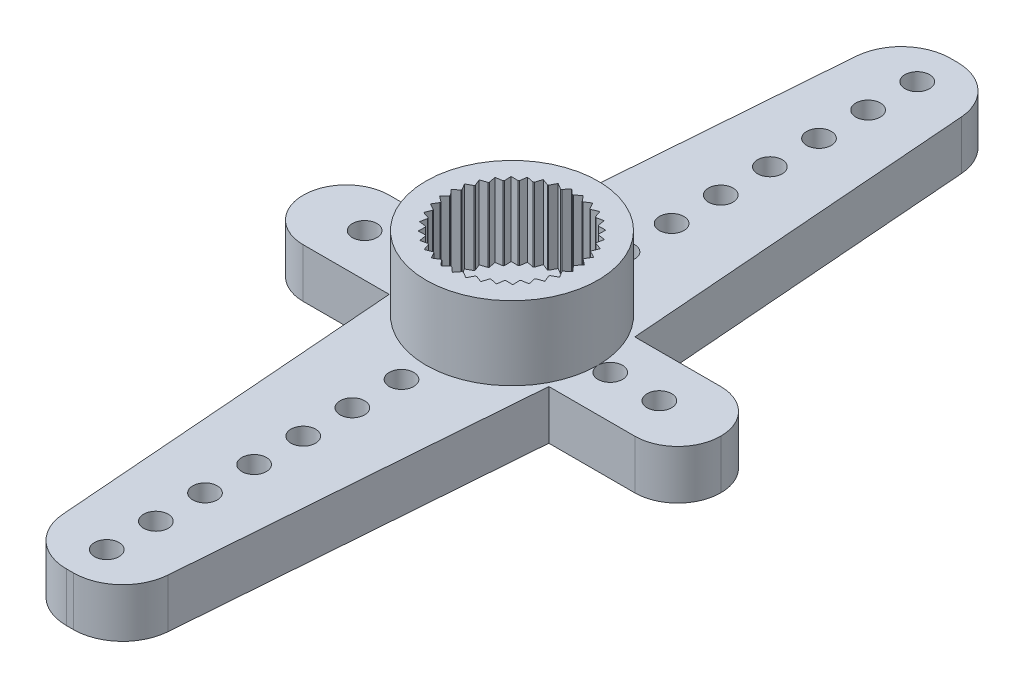
SolidWorks part; units mm, degrees
ref_plane "Front Plane" through (0, 0, 0) normal (0, 0, 1) x (1, 0, 0)
ref_plane "Top Plane" through (0, 0, 0) normal (0, 1, 0) x (1, 0, 0)
ref_plane "Right Plane" through (0, 0, 0) normal (1, 0, 0) x (0, 0, -1)
sketch "Sketch1" plane through (0, 0, 0) normal (0, 1, 0) x (1, 0, 0)
  line L0 (-21.777, 0) -> (33.3507, 0) construction
  line L1 (0, 26.1309) -> (0, -34.4991) construction
  line L2 (-17.4191, 18) -> (29.5794, 18) construction
  line L3 (-18.8664, -18) -> (33.3507, -18) construction
  line L4 (8.5, 26.926) -> (8.5, -27.618) construction
  line L5 (-8.5, 31.6087) -> (-8.5, -32.3009) construction
  line L6 (-24.067, 1.75) -> (35.98, 1.75) construction
  line L7 (-24.067, -1.75) -> (33.3507, -1.75) construction
  line L8 (-3.25, 29.5018) -> (-3.25, -36.5148) construction
  line L9 (3.25, 29.5018) -> (3.25, -33.8811) construction
  line L10 (-2, 29.5018) -> (-2, -51.2631) construction
  line L11 (2, 29.5018) -> (2, -51.2631) construction
  line L12 (-8.5, 1.75) -> (-3.25, 1.75)
  line L13 (-3.25, 1.75) -> (-2, 18)
  line L14 (-2, 18) -> (2, 18)
  line L15 (2, 18) -> (3.25, 1.75)
  line L16 (3.25, 1.75) -> (8.5, 1.75)
  line L17 (8.5, 1.75) -> (8.5, -1.75)
  line L18 (8.5, -1.75) -> (3.25, -1.75)
  line L19 (3.25, -1.75) -> (2, -18)
  line L20 (2, -18) -> (-2, -18)
  line L21 (-2, -18) -> (-3.25, -1.75)
  line L22 (-3.25, -1.75) -> (-8.5, -1.75)
  line L23 (-8.5, -1.75) -> (-8.5, 1.75)
  dimension "D1" = 18
  dimension "D2" = 18
  dimension "D3" = 8.5
  dimension "D4" = 8.5
  dimension "D5" = 1.75
  dimension "D6" = 1.75
  dimension "D7" = 3.25
  dimension "D8" = 3.25
  dimension "D9" = 2
  dimension "D10" = 2
extrude "Boss-Extrude1" add sketch "Sketch1" along normal blind 2
fillet "Fillet1" radius 2 4 edges at (-2, 1, -18) (2, 1, -18) (2, 1, 18) (-2, 1, 18)
fillet "Fillet2" radius 1.75 4 edges at (-8.5, 1, -1.75) (-8.5, 1, 1.75) (8.5, 1, -1.75) (8.5, 1, 1.75)
sketch "Sketch2" plane through (0, 2, 0) normal (0, 1, 0) x (1, 0, 0)
  circle A0 centre (0, 0) radius 3.5
extrude "Boss-Extrude2" add sketch "Sketch2" along normal blind 3
sketch "Sketch3" plane through (0, 0, 0) normal (0, -1, 0) x (-1, 0, 0)
  circle A0 centre (0, 0) radius 2.5
extrude "Cut-Extrude1" cut sketch "Sketch3" against normal blind 1
sketch "Sketch4" plane through (0, 1, 0) normal (0, -1, 0) x (-1, 0, 0)
  circle A0 centre (0, 0) radius 1
extrude "Cut-Extrude2" cut sketch "Sketch4" against normal through all
sketch "Sketch5" plane through (0, 5, 0) normal (0, 1, 0) x (1, 0, 0)
  circle A0 centre (0, 0) radius 2.5
extrude "Cut-Extrude3" cut sketch "Sketch5" against normal blind 3
sketch "Sketch6" plane through (0, 5, 0) normal (0, 1, 0) x (1, 0, 0)
  line L0 (-4.6624, 0) -> (4.5112, 0) construction
  line L1 (-5.0093, 0.3942) -> (0, 0) construction
  line L2 (0, 0) -> (6.4397, -0.5068) construction
  line L3 (0, 0) -> (-6.4046, 1.0144) construction
  line L4 (-2.5, 0) -> (-2.6917, 0.2118)
  line L5 (-2.6917, 0.2118) -> (-2.4692, 0.3911)
  line L6 (-2.4692, 0.3911) -> (-2.5, 0)
  circle A0 centre (0, 0) radius 2.7
  circle A1 centre (0, 0) radius 2.5 construction
  dimension "D1" = 4.5
  dimension "D2" = 4.5
extrude "Cut-Extrude4" cut sketch "Sketch6" against normal blind 3 contours L5 L6 L4
sketch "Sketch8" plane through (0, 0, 0) normal (1, 0, 0) x (0, 0, -1)
  line L0 (0, 0) -> (0, 8.8025) construction
pattern_circular "CirPattern1" count 36 over 360 about axis through (0, 0, 0) along (0, 1, 0) of "Cut-Extrude4"
sketch "Sketch9" plane through (0, 0, 0) normal (0, -1, 0) x (-1, 0, 0)
  circle A0 centre (0, 16.5) radius 0.5
extrude "Cut-Extrude5" cut sketch "Sketch9" against normal through all contours A0
sketch "Sketch10" plane through (0, 0, 0) normal (0, -1, 0) x (-1, 0, 0)
  line L0 (0, 13.2867) -> (0, -8.4466) construction
pattern_linear "LPattern1" count 7 spacing 2 along (0, 0, 1) of "Cut-Extrude5"
mirror "Mirror1" about plane through (0, 0, 0) normal (0, 0, 1) of "LPattern1"
sketch "Sketch11" plane through (0, 0, 0) normal (0, -1, 0) x (-1, 0, 0)
  circle A0 centre (-6, 0) radius 0.5
extrude "Cut-Extrude6" cut sketch "Sketch11" against normal through all
pattern_linear "LPattern2" count 2 spacing 2 along (-1, 0, 0) of "Cut-Extrude6"
mirror "Mirror2" about plane through (0, 0, 0) normal (1, 0, 0) of "LPattern2"
